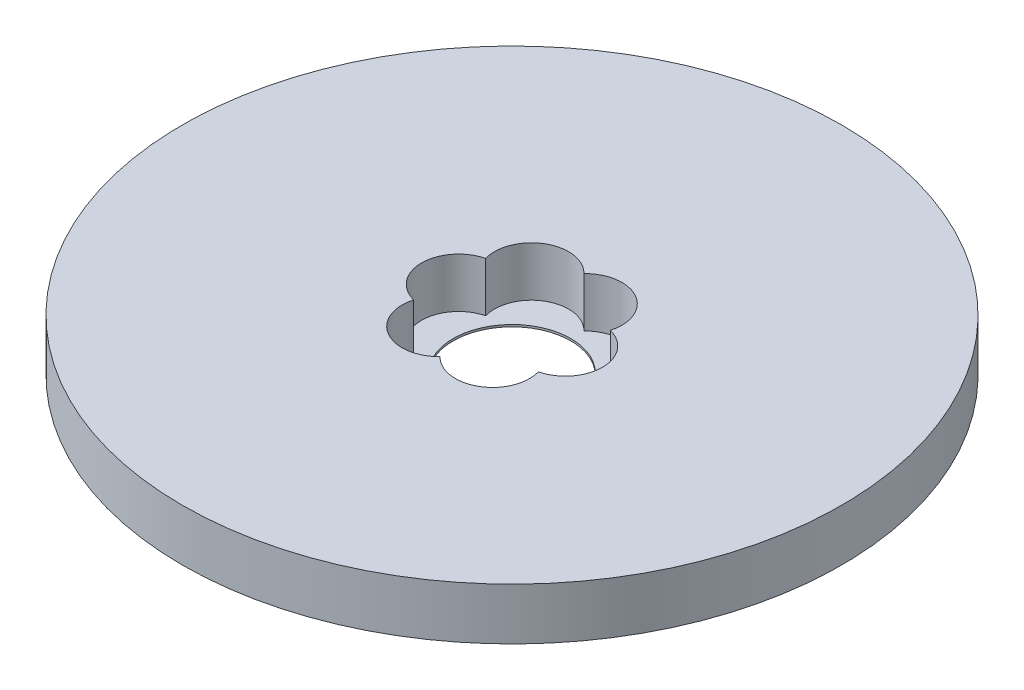
SolidWorks part; units mm, degrees
ref_plane "Front Plane" through (0, 0, 0) normal (0, 0, 1) x (1, 0, 0)
ref_plane "Top Plane" through (0, 0, 0) normal (0, 1, 0) x (1, 0, 0)
ref_plane "Right Plane" through (0, 0, 0) normal (1, 0, 0) x (0, 0, -1)
sketch "Sketch1" plane through (0, 0, 0) normal (0, 1, 0) x (1, 0, 0)
  circle A0 centre (0, 0) radius 70
  dimension "FLANGE_OD" = 140
extrude "Boss-Extrude1" add sketch "Sketch1" along normal blind 11
sketch "Sketch2" plane through (0, 0, 0) normal (0, 1, 0) x (1, 0, 0)
  circle A0 centre (0, 0) radius 12.5
  dimension "BORE_D" = 25
extrude "Cut-Extrude1" cut sketch "Sketch2" along normal through all
sketch "Sketch3" plane through (0, 11, 0) normal (0, 1, 0) x (1, 0, 0)
  circle A0 centre (0, 0) radius 11.3343 construction
  circle A1 centre (-11.3343, 0) radius 7.8746
  dimension "BOLT_D" = 15.7492
  dimension "BOLT_PCD" = 22.6686
extrude "Cut-Extrude2" cut sketch "Sketch3" against normal blind 10.5623
pattern_circular "CirPattern1" count 6 over 360 about axis through (0, 0, 0) along (0, 1, 0) of "Cut-Extrude2"
